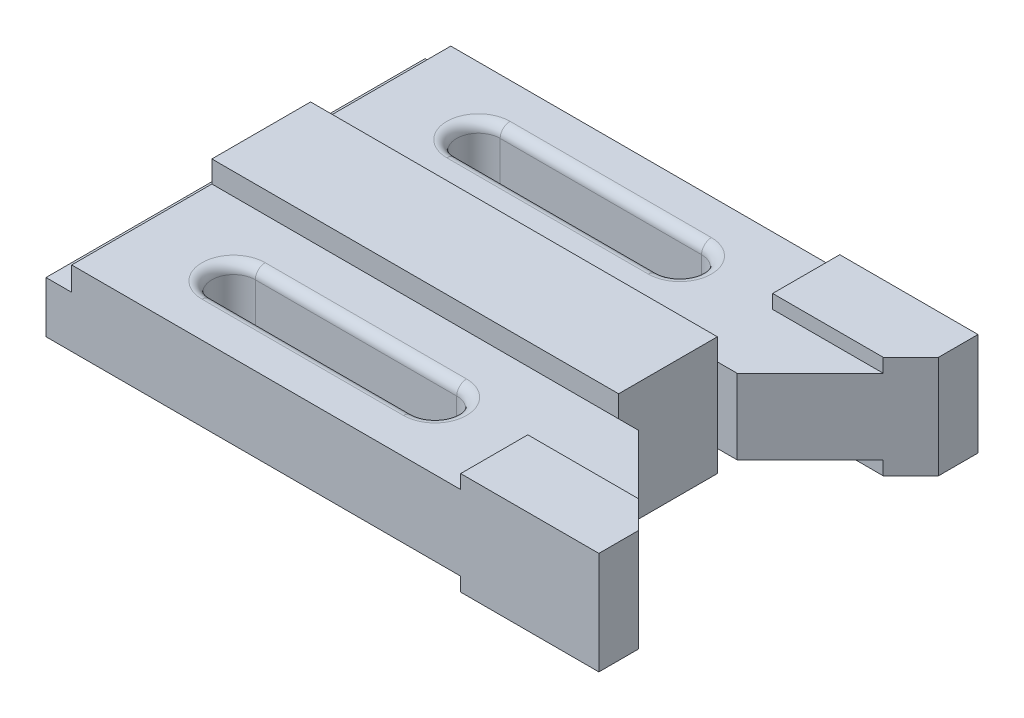
SolidWorks part; units mm, degrees
material "1060 Alloy"
ref_plane "Front Plane" through (0, 0, 0) normal (0, 0, 1) x (1, 0, 0)
ref_plane "Top Plane" through (0, 0, 0) normal (0, 1, 0) x (1, 0, 0)
ref_plane "Right Plane" through (0, 0, 0) normal (1, 0, 0) x (0, 0, -1)
sketch "Sketch1" plane through (0, 0, 0) normal (0, 1, 0) x (1, 0, 0)
  line L0 (0, 0) -> (109.5, 0) construction
  line L1 (0, 48) -> (0, -48)
  line L2 (0, -48) -> (140, -48)
  line L3 (140, -48) -> (140, -38)
  line L4 (140, -38) -> (114.5, -12.5)
  line L5 (114.5, -12.5) -> (109.5, -12.5)
  line L6 (109.5, -12.5) -> (109.5, 12.5)
  line L7 (105, -48) -> (105, -31)
  line L8 (105, -31) -> (133, -31)
  line L9 (109.5, -12.5) -> (0, -12.5)
  line L10 (30.5, -31) -> (81.5, -31) construction
  line L11 (30.5, -25.5) -> (81.5, -25.5)
  line L12 (30.5, -36.5) -> (81.5, -36.5)
  line L13 (109.5, 12.5) -> (0, 12.5)
  line L14 (105, 31) -> (133, 31)
  line L15 (105, 48) -> (105, 31)
  line L16 (114.5, 12.5) -> (109.5, 12.5)
  line L17 (140, 38) -> (114.5, 12.5)
  line L18 (140, 48) -> (140, 38)
  line L19 (0, 48) -> (140, 48)
  line L20 (30.5, 31) -> (81.5, 31) construction
  line L21 (30.5, 25.5) -> (81.5, 25.5)
  line L22 (30.5, 36.5) -> (81.5, 36.5)
  arc A0 (30.5, -25.5) -> (30.5, -36.5) centre (30.5, -31) ccw
  arc A1 (81.5, -36.5) -> (81.5, -25.5) centre (81.5, -31) ccw
  arc A2 (30.5, 25.5) -> (30.5, 36.5) centre (30.5, 31) cw
  arc A3 (81.5, 36.5) -> (81.5, 25.5) centre (81.5, 31) cw
  point P14 (56, -31)
  point P30 (56, 31)
  dimension "D9" = 5.5
  dimension "D1" = 140
  dimension "D2" = 51
  dimension "D3" = 35
  dimension "D4" = 35.5
  dimension "D5" = 17
  dimension "D6" = 10
  dimension "D7" = 48
  dimension "D8" = 45
  dimension "D10" = 30.5
  dimension "D11" = 30.5
extrude "Boss-Extrude1" add sketch "Sketch1" along normal mid plane 30 contours L6 L13 L1 L9 region at (54.75, 0, 0)
extrude "Boss-Extrude2" add sketch "Sketch1<3>" along normal mid plane 19 separate body contours L5 L9 L1 L2 L7 L8 L4 A1 L12 A0 L11 | L19 L1 L13 L16 L17 L14 L15 L22 A3 L21 A2 region at (52.5, 0, -46.6234) region at (54.75, 0, 13.8766)
sketch "Sketch1<3>" plane through (0, 0, 0) normal (0, 1, 0) x (1, 0, 0) same geometry as "Sketch1"
extrude "Boss-Extrude3" add sketch "Sketch1<4>" along normal mid plane 26 contours L8 L7 L2 L3 L4 | L19 L15 L14 L17 L18 region at (121.8487, 0, -39.7648) region at (121.8487, 0, 39.7648)
sketch "Sketch1<4>" plane through (0, 0, 0) normal (0, 1, 0) x (1, 0, 0) same geometry as "Sketch1"
fillet "Fillet1" radius 2.5 4 edges at (25, 9.5, -31) (87, 9.5, -31) (56, 9.5, -25.5) (56, 9.5, -36.5)
fillet "Fillet2" radius 2.5 4 edges at (25, 9.5, 31) (87, 9.5, 31) (56, 9.5, 36.5) (56, 9.5, 25.5)
fillet "Fillet3" radius 2.5 4 edges at (87, -9.5, -31) (25, -9.5, -31) (56, -9.5, -25.5) (56, -9.5, -36.5)
fillet "Fillet4" radius 2.5 4 edges at (87, -9.5, 31) (25, -9.5, 31) (56, -9.5, 36.5) (56, -9.5, 25.5)
sketch "Sketch2" plane through (0, 15, 0) normal (0, 1, 0) x (1, 0, 0)
  line L0 (0, 12.5) -> (0, -12.5) construction
  line L1 (0, -48) -> (6.5, -48)
  line L2 (0, -48) -> (0, 48)
  line L3 (0, 48) -> (6.5, 48)
  line L4 (6.5, -48) -> (6.5, 48)
  line L5 (0, 48) -> (105, 48) construction
  dimension "D1" = 96
  dimension "D2" = 6.5
extrude "Cut-Extrude1" cut sketch "Sketch2" against normal blind 11.5
equation "\"A\"= 140mm"
equation "\"B\"= 51mm"
equation "\"C\"= 45deg"
